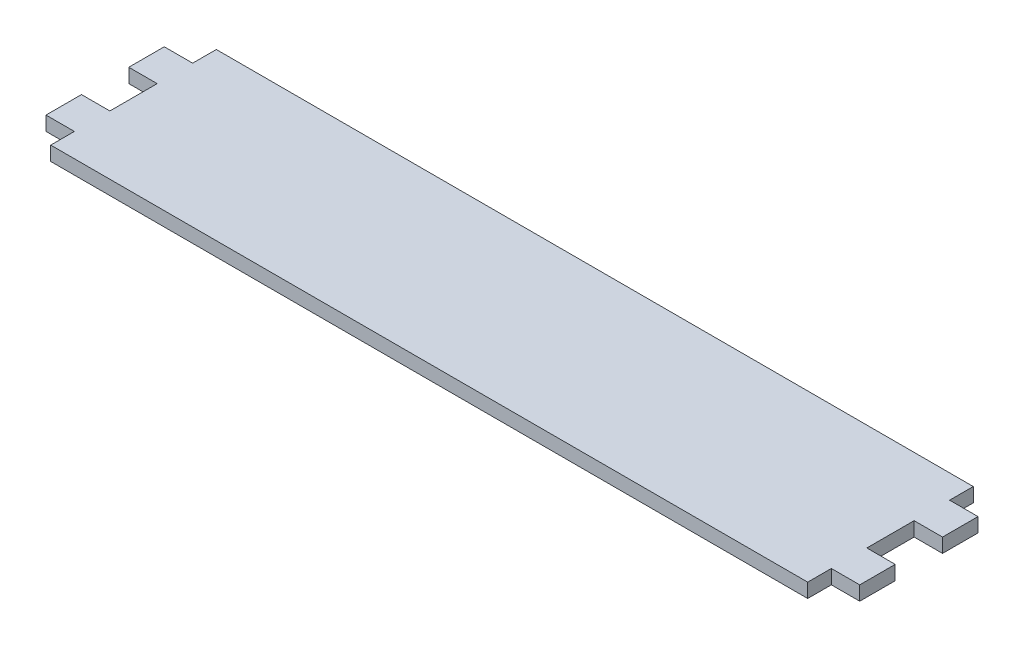
SolidWorks part; units mm, degrees
ref_plane "Front" through (0, 0, 0) normal (0, 0, 1) x (1, 0, 0)
ref_plane "Top" through (0, 0, 0) normal (0, 1, 0) x (1, 0, 0)
ref_plane "Right" through (0, 0, 0) normal (1, 0, 0) x (0, 0, -1)
sketch "Skizze1" plane through (0, 0, 0) normal (0, 1, 0) x (1, 0, 0)
  line L1 (160, 35) -> (-160, 35)
  line L2 (160, 35) -> (160, -35)
  line L3 (160, -35) -> (-160, -35)
  line L4 (-160, 35) -> (-160, -35)
  line L5 (160, 35) -> (-160, -35) construction
  line L6 (160, -35) -> (-160, 35) construction
  point P0 (0, 0)
  dimension "D1" = 320
  dimension "D2" = 70
extrude "Grundform" add sketch "Skizze1" along normal blind 6
sketch "Skizze2" plane through (0, 6, 0) normal (0, 1, 0) x (1, 0, 0)
  line L0 (0, 35) -> (0, 15) construction
  line L1 (160, 35) -> (-160, 35) construction
  line L2 (0, 15) -> (0, -15) construction
  line L3 (0, -15) -> (0, -35) construction
  line L4 (-160, -35) -> (160, -35) construction
  line L5 (0, -15) -> (-31, -15) construction
  line L6 (-31, -15) -> (-62, -15) construction
  line L7 (-62, -15) -> (-93, -15) construction
  line L8 (-93, -15) -> (-124, -15) construction
  line L10 (-15.5, 15) -> (-15.5, -15) construction
  line L11 (-15.5, 15) -> (0, 15) construction
  line L12 (-15.5, 15) -> (-46.5, 15) construction
  line L13 (-46.5, 15) -> (-77.5, 15) construction
  line L14 (-77.5, 15) -> (-108.5, 15) construction
  line L15 (-108.5, 15) -> (-139.5, 15) construction
  circle A0 centre (0, -15) radius 13.25
  circle A1 centre (-31, -15) radius 13.25
  circle A2 centre (-62, -15) radius 13.25
  circle A3 centre (-93, -15) radius 13.25
  circle A4 centre (-124, -15) radius 13.25
  circle A6 centre (-15.5, 15) radius 13.25
  circle A7 centre (-46.5, 15) radius 13.25
  circle A8 centre (-77.5, 15) radius 13.25
  circle A9 centre (-108.5, 15) radius 13.25
  circle A10 centre (-139.5, 15) radius 13.25
  circle A12 centre (124, -15) radius 13.25
  circle A13 centre (93, -15) radius 13.25
  circle A14 centre (62, -15) radius 13.25
  circle A15 centre (31, -15) radius 13.25
  circle A16 centre (139.5, 15) radius 13.25
  circle A17 centre (108.5, 15) radius 13.25
  circle A18 centre (77.5, 15) radius 13.25
  circle A19 centre (46.5, 15) radius 13.25
  circle A20 centre (15.5, 15) radius 13.25
  dimension "D1" = 26.5
  dimension "D2" = 20
  dimension "D3" = 31
extrude "Flaschendurchbruch" [suppressed] cut sketch "Skizze2" against normal through all
ref_plane "Ebene1" through (0, 0, 0) normal (1, 0, 0) x (0, 0, -1)
sketch "Skizze3" plane through (-160, 0, 0) normal (-1, 0, 0) x (0, 0, 1)
  line L0 (-35, 6) -> (35, 6) construction
  line L1 (-25, 6) -> (-10, 6)
  line L2 (-25, 6) -> (-25, 0)
  line L3 (-25, 0) -> (-10, 0)
  line L4 (-10, 6) -> (-10, 0)
  line L5 (-35, 0) -> (35, 0) construction
  line L6 (0, 0) -> (0, 6) construction
  line L11 (10, 6) -> (10, 0)
  line L12 (25, 0) -> (10, 0)
  line L13 (25, 6) -> (25, 0)
  line L14 (25, 6) -> (10, 6)
  dimension "D1" = 20
  dimension "D2" = 15
extrude "Aufsatz-Linear austragen2" add sketch "Skizze3" along normal blind 12
mirror "Spiegeln1" about plane through (0, 0, 0) normal (1, 0, 0) of "Aufsatz-Linear austragen2"
